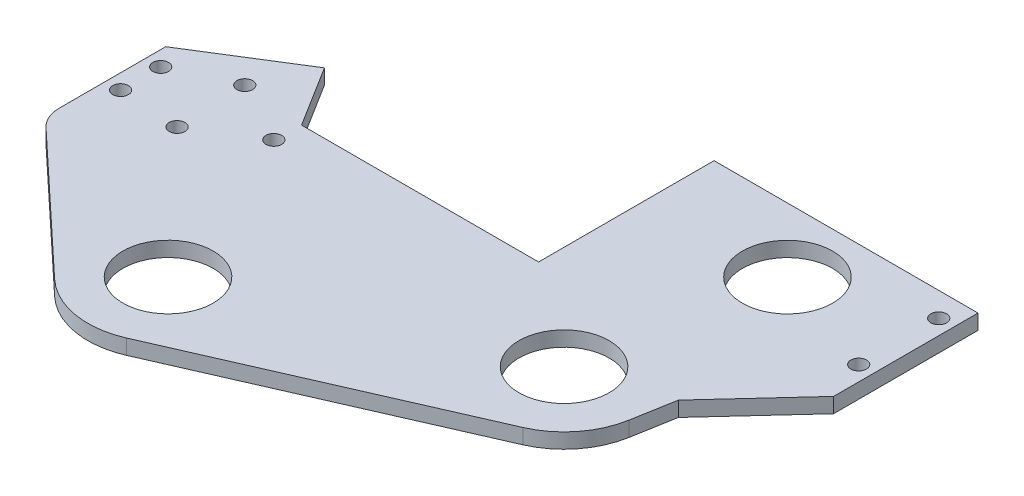
SolidWorks part; units mm, degrees
ref_plane "Front Plane" through (0, 0, 0) normal (0, 0, 1) x (1, 0, 0)
ref_plane "Top Plane" through (0, 0, 0) normal (0, 1, 0) x (1, 0, 0)
ref_plane "Right Plane" through (0, 0, 0) normal (1, 0, 0) x (0, 0, -1)
sketch "Sketch1" plane through (0, 0, 0) normal (0, 1, 0) x (1, 0, 0)
  line L1 (-62.0695, -79.8953) -> (25.163, -41.6958)
  line L5 (39.9361, -22.8907) -> (42.2711, -9.5867)
  line L6 (42.2711, -9.5867) -> (65.827, 16.0128)
  line L12 (-135.7856, -31.9357) -> (-135.7856, 6.1643)
  line L16 (-92.7763, 6.1642) -> (-17.7344, 6.1642)
  line L17 (-135.7856, -31.9357) -> (-89.6201, -75.1681)
  line L19 (65.8268, 61.7268) -> (-17.7344, 61.7268)
  line L20 (65.827, 16.0128) -> (65.8268, 61.7268)
  line L22 (-17.7344, 61.7268) -> (-17.7344, 6.1642)
  line L23 (-135.7856, 6.1643) -> (-104.8541, 25.4925)
  line L24 (-205.1732, 186.0357) -> (-71.6499, -27.6449) construction
  line L25 (-104.8541, 25.4925) -> (-92.7763, 6.1642)
  circle A0 centre (25.8218, 41.4126) radius 14.29
  circle A1 centre (15.0126, -18.5165) radius 14.29
  circle A2 centre (-72.2583, -56.6285) radius 14.29
  arc A4 (39.9361, -22.8907) -> (25.163, -41.6958) centre (15.0127, -18.5164) cw
  arc A6 (-62.0695, -79.8953) -> (-89.6201, -75.1681) centre (-72.2582, -56.6283) cw
  point P11 (-62.0695, -79.8953)
extrude "Boss-Extrude1" add sketch "Sketch1" along normal blind 4.7625
fillet "Fillet1" radius 10 1 edges at (-135.7856, 2.3813, 31.9357)
hole_wizard "#10 Clearance Hole1" positions "Sketch2" profile "Sketch3" hole size "#10" standard "ANSI Inch" end condition through all
sketch "Sketch2" plane through (0, 4.7625, 0) normal (0, 1, 0) x (1, 0, 0)
  point P0 (61.0644, 54.0575)
  point P3 (61.0644, 28.7127)
  point P7 (-131.0231, -0.1858)
  point P10 (-131.0231, -12.8858)
sketch "Sketch3" plane through (61.0644, 4.7625, -54.0575) normal (1, 0, 0) x (0, 0, 1)
  line L0 (0, 0) -> (0, 4.7625)
  line L1 (0, 4.7625) -> (2.4892, 4.7625)
  line L2 (2.4892, 4.7625) -> (2.4892, 0)
  line L5 (2.4892, 0) -> (0, 0)
  line L11 (0, -6.35) -> (0, 107.95) construction
  dimension "Thru Hole Dia." = 4.9784
  dimension "Thru Hole Depth" = 4.7625
sketch "Sketch4" plane through (0, 4.7625, 0) normal (0, 1, 0) x (1, 0, 0)
  line L0 (-72.2583, -56.6285) -> (-102.5433, -8.1626) construction
  line L1 (-102.5433, -8.1626) -> (-93.1194, -2.2738) construction
  line L2 (-102.5433, -8.1626) -> (-111.9673, -14.0514) construction
  line L3 (-102.5433, -8.1626) -> (-112.7326, 8.1435) construction
  line L4 (-102.5433, -8.1626) -> (-186.6684, 126.4648) construction
  line L5 (65.8269, 41.4127) -> (65.8269, 28.7127) construction
  dimension "D1" = 57.15
  dimension "D2" = 22.225
  dimension "D3" = 32
hole_wizard "#10 Clearance Hole2" positions "Sketch5" profile "Sketch6" hole size "#10" standard "ANSI Inch" end condition through all
sketch "Sketch5" plane through (0, 4.7625, 0) normal (0, 1, 0) x (1, 0, 0)
  point P0 (-111.9673, -14.0514)
  point P3 (-93.1194, -2.2738)
  point P7 (-112.7326, 8.1435)
sketch "Sketch6" plane through (-111.9673, 4.7625, 14.0514) normal (1, 0, 0) x (0, 0, 1)
  line L0 (0, 0) -> (0, 4.7625)
  line L1 (0, 4.7625) -> (2.4892, 4.7625)
  line L2 (2.4892, 4.7625) -> (2.4892, 0)
  line L5 (2.4892, 0) -> (0, 0)
  line L11 (0, -6.35) -> (0, 107.95) construction
  dimension "Thru Hole Dia." = 4.9784
  dimension "Thru Hole Depth" = 4.7625
